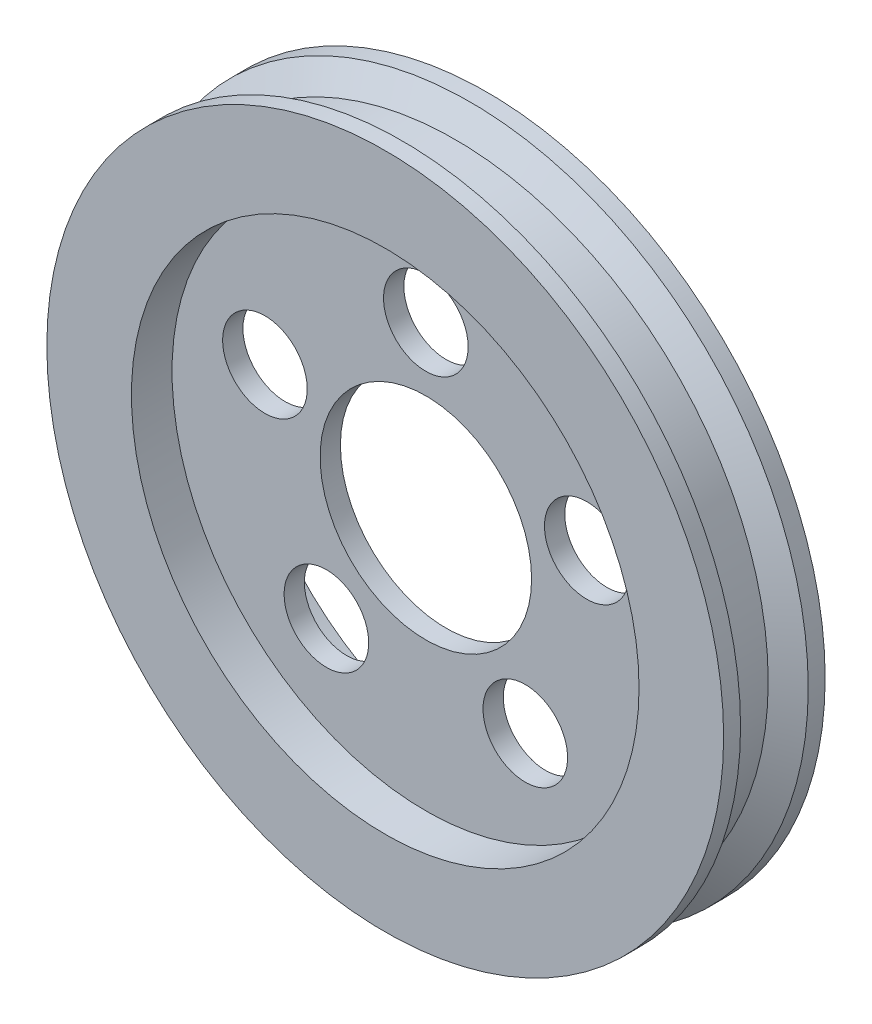
SolidWorks part; units mm, degrees
ref_plane "Front Plane" through (0, 0, 0) normal (0, 0, 1) x (1, 0, 0)
ref_plane "Top Plane" through (0, 0, 0) normal (0, 1, 0) x (1, 0, 0)
ref_plane "Right Plane" through (0, 0, 0) normal (1, 0, 0) x (0, 0, -1)
sketch "Sketch1" plane through (0, 0, 0) normal (0, 0, 1) x (1, 0, 0)
  circle A0 centre (0, 0) radius 4
  circle A1 centre (0, 0) radius 20
  dimension "D1" = 8
  dimension "20" = 40
extrude "Boss-Extrude1" add sketch "Sketch1" along normal mid plane 6
sketch "Sketch3" plane through (0, 0, 3) normal (0, 0, 1) x (1, 0, 0)
  circle A0 centre (0, 0) radius 15
  dimension "D1" = 30
extrude "Cut-Extrude1" cut sketch "Sketch3" against normal blind 2.4 contours A0
mirror "Mirror1" about plane through (0, 0, 0) normal (0, 0, 1) of "Cut-Extrude1"
sketch "Sketch4" plane through (0, 0, 0.6) normal (0, 0, 1) x (1, 0, 0)
  circle A0 centre (0, 10) radius 2.5
  dimension "D1" = 10
  dimension "D2" = 5
extrude "Cut-Extrude2" cut sketch "Sketch4" against normal through all
pattern_circular "CirPattern1" count 5 over 360 about axis through (0, 0, 3) along (0, 0, -1) of "Cut-Extrude2" reverse direction yes
sketch "Sketch5" plane through (0, 0, 0) normal (0, 1, 0) x (1, 0, 0)
  line L0 (0, 0) -> (0, 6.988) construction
  line L1 (20, 2) -> (18.5, 1.134)
  line L2 (20, -3) -> (20, 3) construction
  line L3 (18.5, 1.134) -> (18.5, -1.134)
  line L4 (18.5, -1.134) -> (20, -2)
  line L5 (20, 2) -> (20, -2)
  dimension "D1" = 1.5
  dimension "D2" = 1
  dimension "D3" = 1
  dimension "D4" = 60
  dimension "D5" = 60
revolve "Cut-Revolve1" cut sketch "Sketch5" angle 360 about L0
sketch "Sketch14" plane through (0, 0, 0.6) normal (0, 0, 1) x (1, 0, 0)
  circle A0 centre (0, 0) radius 5
  dimension "D1" = 10
extrude "Boss-Extrude3" add sketch "Sketch14" along normal blind 1 and the other way blind 2 contours A0
sketch "Sketch16" plane through (0, 0, 1.6) normal (0, 0, 1) x (1, 0, 0)
  circle A0 centre (0, 0) radius 6.25
  dimension "D1" = 12.5
extrude "Cut-Extrude3" cut sketch "Sketch16" against normal through all
